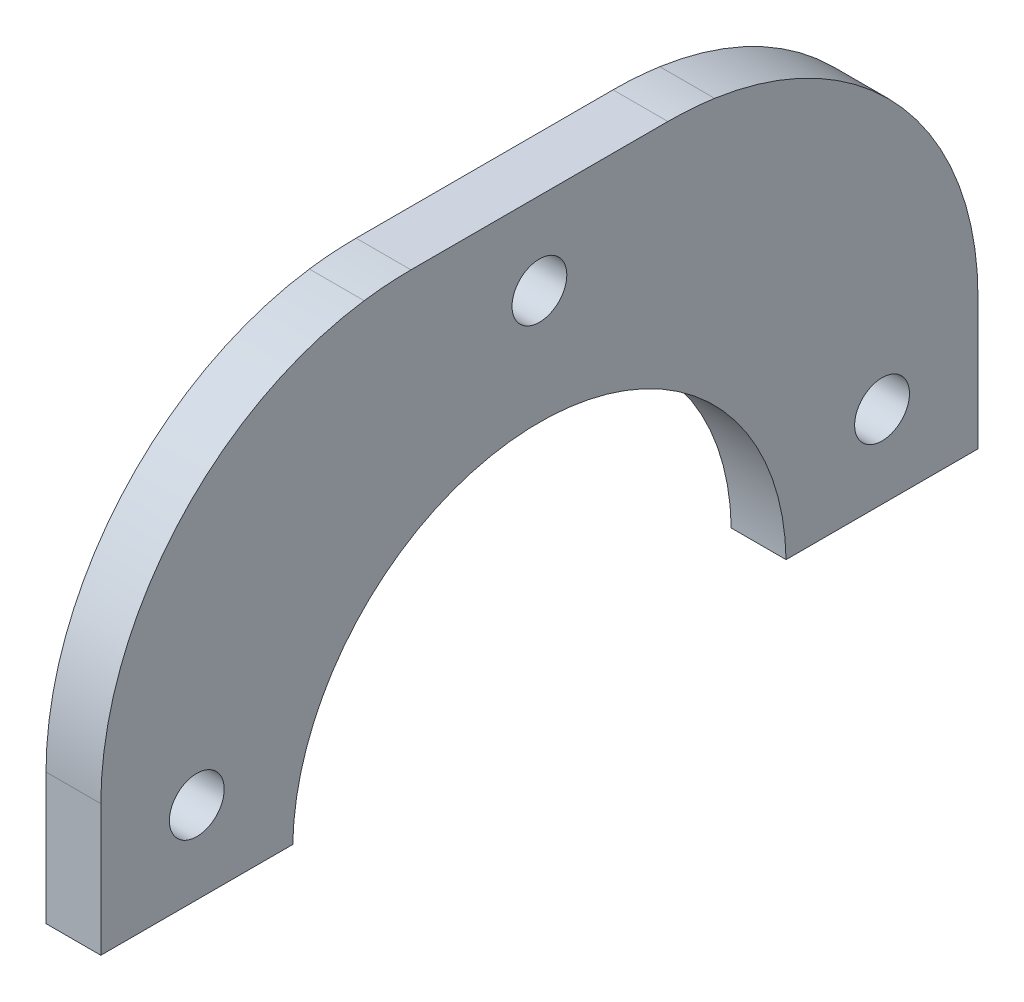
SolidWorks part; units mm, degrees
material "6061 Alloy"
ref_plane "Front Plane" through (0, 0, 0) normal (0, 0, 1) x (1, 0, 0)
ref_plane "Top Plane" through (0, 0, 0) normal (0, 1, 0) x (1, 0, 0)
ref_plane "Right Plane" through (0, 0, 0) normal (1, 0, 0) x (0, 0, -1)
sketch "Sketch1" plane through (0, 0, 0) normal (1, 0, 0) x (0, 0, -1)
  line L4 (0, 12.7) -> (0, 4.6747) construction
  line L5 (-25.4, -12.7) -> (25.4, -12.7)
  line L6 (-25.4, -12.7) -> (-25.4, 0)
  line L7 (-7.4395, 12.7) -> (7.4395, 12.7)
  line L8 (25.4, -12.7) -> (25.4, 0)
  line L9 (-25.4, -12.7) -> (25.4, 12.7) construction
  line L10 (-25.4, 12.7) -> (25.4, -12.7) construction
  line L11 (-25.4, 0) -> (-25.4, 12.7) construction
  line L12 (25.4, 0) -> (25.4, 12.7) construction
  arc A0 (-25.4, 0) -> (-7.4395, 12.7) centre (-7.4395, -6.35) cw
  arc A1 (25.4, 0) -> (7.4395, 12.7) centre (7.4395, -6.35) ccw
  point P0 (0, 0)
  point P14 (7.4395, 14.0801)
  dimension "D3" = 19.05
  dimension "D4" = 12.7
  dimension "D1" = 25.4
  dimension "D5" = 50.8
extrude "Boss-Extrude1" add sketch "Sketch1" along normal blind 3.175
sketch "Sketch2" plane through (3.175, 0, 0) normal (1, 0, 0) x (0, 0, -1)
  line L1 (-25.4, -12.7) -> (25.4, -12.7) construction
  circle A0 centre (0, -12.954) radius 14.2875
  point P2 (0, -14.1947)
  point P4 (0, 0)
  dimension "D1" = 28.575
  dimension "D2" = 0.254
extrude "Cut-Extrude1" cut sketch "Sketch2" against normal through all
hole_wizard "1/8 (0.125) Diameter Hole1" positions "Sketch3" profile "Sketch4" hole size "1/8" standard "ANSI Inch"
sketch "Sketch3" plane through (3.175, 0, 0) normal (1, 0, 0) x (0, 0, -1)
  line L0 (-25.4, -12.7) -> (-14.2852, -12.7) construction
  line L1 (7.4395, 12.7) -> (-7.4395, 12.7) construction
  line L2 (14.2852, -12.7) -> (25.4, -12.7) construction
  circle A0 centre (0, 7.9375) radius 3.175 construction
  circle A1 centre (-19.8426, -7.9375) radius 3.175 construction
  circle A2 centre (19.8426, -7.9375) radius 3.175 construction
  point P0 (-19.8426, -7.9375)
  point P2 (0, 7.9375)
  point P4 (19.8426, -7.9375)
  point P12 (0, 12.7)
  point P13 (-19.8426, -12.7)
  point P16 (19.8426, -12.7)
  dimension "D3" = 6.35
  dimension "D1" = 4.7625
  dimension "D2" = 4.7625
sketch "Sketch4" plane through (3.175, -7.9375, 19.8426) normal (0, 1, 0) x (0, 0, -1)
  line L0 (0, 0) -> (0, 19.9559)
  line L1 (0, 19.9559) -> (1.5875, 19.002)
  line L2 (1.5875, 19.002) -> (1.5875, 0)
  line L5 (1.5875, 0) -> (0, 0)
  line L10 (0, 19.9559) -> (-1.5875, 19.002) construction
  line L11 (0, -6.35) -> (0, 107.95) construction
  dimension "Hole Dia." = 3.175
  dimension "Hole Depth" = 19.002
  dimension "Drill Angle" = 118
fillet "Fillet1" radius 17.78 2 edges at (1.5875, 0, 25.4) (1.5875, 0, -25.4)
